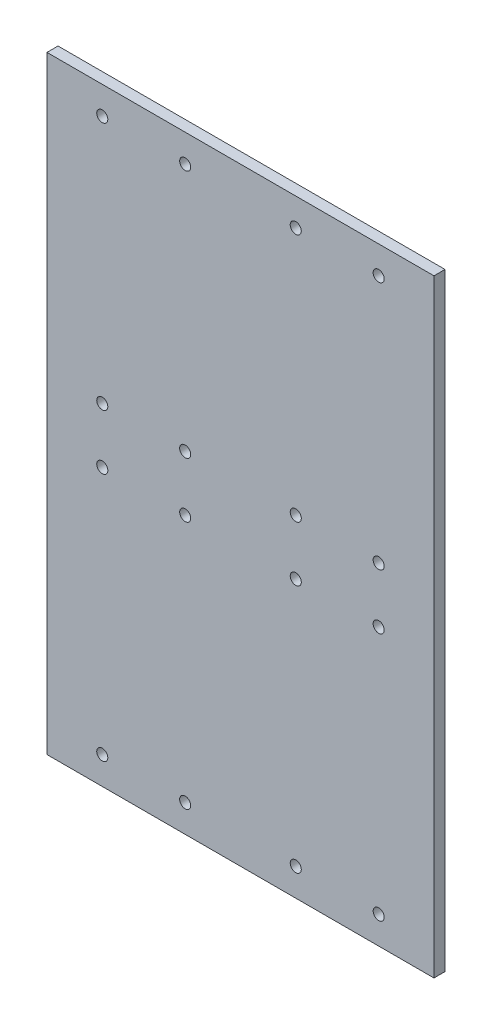
SolidWorks part; units mm, degrees
ref_plane "正面" through (0, 0, 0) normal (0, 0, 1) x (1, 0, 0)
ref_plane "平面" through (0, 0, 0) normal (0, 1, 0) x (1, 0, 0)
ref_plane "右側面" through (0, 0, 0) normal (1, 0, 0) x (0, 0, -1)
sketch "ｽｹｯﾁ1" plane through (0, 0, 0) normal (0, 0, 1) x (1, 0, 0)
  line L1 (35, -55) -> (-35, -55)
  line L2 (35, -55) -> (35, 55)
  line L3 (35, 55) -> (-35, 55)
  line L4 (-35, -55) -> (-35, 55)
  line L5 (35, -55) -> (-35, 55) construction
  line L6 (35, 55) -> (-35, -55) construction
  point P0 (0, 0)
  dimension "D1" = 110
  dimension "D2" = 70
extrude "ﾎﾞｽ - 押し出し1" add sketch "ｽｹｯﾁ1" along normal blind 2 contours L4 L1 L2 L3
sketch "ｽｹｯﾁ2" plane through (0, 0, 0) normal (0, 0, 1) x (1, 0, 0)
  line L1 (25, -50) -> (10, -50) construction
  line L2 (25, -50) -> (25, -5) construction
  line L3 (25, -5) -> (10, -5) construction
  line L4 (10, -50) -> (10, -5) construction
  line L5 (25, -50) -> (10, -5) construction
  line L6 (25, -5) -> (10, -50) construction
  line L13 (35, -55) -> (-35, -55) construction
  circle A0 centre (10, -5) radius 1
  circle A1 centre (25, -5) radius 1
  circle A2 centre (10, -50) radius 1
  circle A3 centre (25, -50) radius 1
  point P0 (17.5, -27.5)
  dimension "D1" = 2
  dimension "D2" = 45
  dimension "D3" = 15
  dimension "D4" = 10
  dimension "D5" = 5
extrude "ｶｯﾄ - 押し出し4" cut sketch "ｽｹｯﾁ2" against normal through all both and the other way through all
mirror "ﾐﾗｰ2" about plane through (0, 0, 0) normal (1, 0, 0) of "ｶｯﾄ - 押し出し4"
mirror "ﾐﾗｰ6" about plane through (0, 0, 0) normal (0, 1, 0) of "ﾐﾗｰ2"
